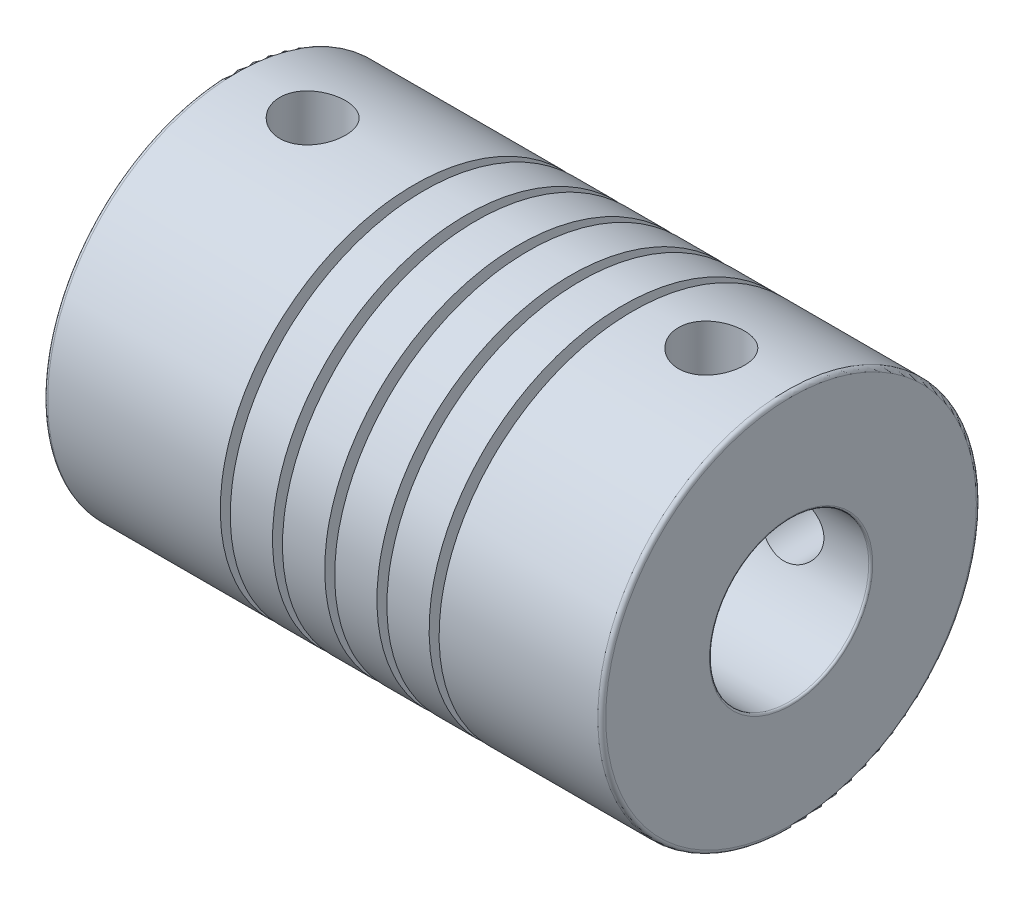
SolidWorks part; units mm, degrees
ref_plane "Front Plane" through (0, 0, 0) normal (0, 0, 1) x (1, 0, 0)
ref_plane "Top Plane" through (0, 0, 0) normal (0, 1, 0) x (1, 0, 0)
ref_plane "Right Plane" through (0, 0, 0) normal (1, 0, 0) x (0, 0, -1)
sketch "Sketch1" plane through (0, 0, 0) normal (1, 0, 0) x (0, 0, -1)
  circle A0 centre (0, 0) radius 9.5
  circle A1 centre (0, 0) radius 2.5
  dimension "D1" = 19
  dimension "D2" = 5
extrude "Boss-Extrude1" add sketch "Sketch1" along normal blind 28 and the other way blind 0.01
sketch "Sketch2" plane through (28, 0, 0) normal (1, 0, 0) x (0, 0, -1)
  circle A0 centre (0, 0) radius 4
  dimension "D1" = 8
extrude "Cut-Extrude1" cut sketch "Sketch2" against normal blind 18 contours A0
sketch "Sketch3" plane through (0, 0, 0) normal (0, 0, 1) x (1, 0, 0)
  line L0 (7.49, 9.5) -> (7.49, -9.5) construction
  line L1 (28, 9.5) -> (-0.01, 9.5) construction
  line L2 (-0.01, -9.5) -> (28, -9.5) construction
  line L3 (20.5, 9.5) -> (20.5, -9.5) construction
  line L4 (-0.01, 9.5) -> (-0.01, -9.5) construction
  line L5 (28, -9.5) -> (28, 9.5) construction
  line L11 (20.5, 9.5) -> (20, 9.5)
  line L12 (20.5, 9.5) -> (20.5, 4)
  line L13 (20.5, 4) -> (20, 4)
  line L14 (20, 9.5) -> (20, 4)
  dimension "D1" = 7.5
  dimension "D2" = 7.5
  dimension "D5" = 0.5
  dimension "D6" = 5.5
ref_plane "Plane4" through (20.59, 0, 0) normal (-1, 0, 0) x (0, 0, 1)
sketch "Sketch7" plane through (20.59, 0, 0) normal (-1, 0, 0) x (0, 0, 1)
  circle A0 centre (0, 0) radius 9.5
  dimension "D1" = 19
curve "Helix/Spiral1" pitch 2.62 height 13.1 radius 9.5 left hand yes centre (20.59, 0, 0) axis (-1, 0, 0) start towards (0, 0.7071, -0.7071)
sweep "Cut-Sweep2" cut profiles "Sketch3" path "Helix/Spiral1"
sketch "Sketch8" plane through (0, 0, 0) normal (0, 0, 1) x (1, 0, 0)
  line L0 (0, 0) -> (28, 0) construction
  line L1 (28, -9.5) -> (28, 9.5) construction
  circle A0 centre (4, 0) radius 1.65
  circle A1 centre (24, 0) radius 1.65
  dimension "D1" = 3.3
  dimension "D2" = 4
  dimension "D3" = 4
extrude "Cut-Extrude3" cut sketch "Sketch8" against normal blind 10
sketch "Sketch10" plane through (0, 0, 0) normal (0, 1, 0) x (1, 0, 0)
  line L0 (-0.01, 0) -> (28, 0) construction
  line L1 (-0.01, 9.5) -> (-0.01, -9.5) construction
  line L2 (28, -9.5) -> (28, 9.5) construction
  circle A0 centre (3.99, 0) radius 1.65
  circle A1 centre (24, 0) radius 1.65
  dimension "D1" = 3.3
  dimension "D2" = 4
  dimension "D3" = 4
extrude "Cut-Extrude4" cut sketch "Sketch10" along normal blind 11
fillet "Fillet1" radius 0.2 2 edges at (-0.01, 0, -9.5) (28, 0, -9.5)
fillet "Fillet2" radius 0.1 2 edges at (-0.01, 0, -2.5) (28, 0, -4)
